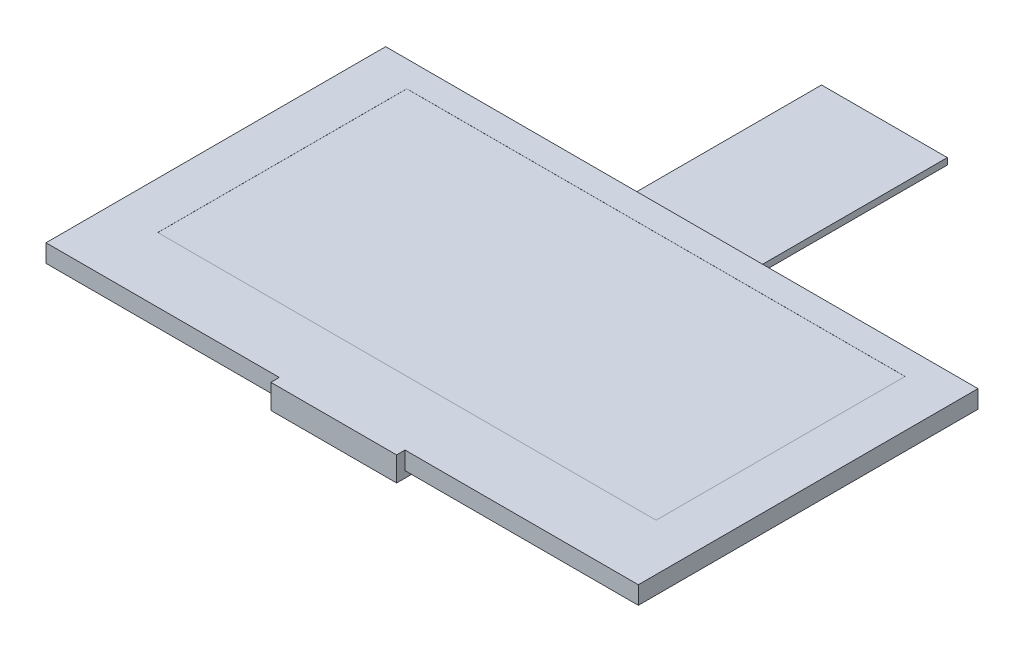
SolidWorks part; units mm, degrees
ref_plane "前视基准面" through (0, 0, 0) normal (0, 0, 1) x (1, 0, 0)
ref_plane "上视基准面" through (0, 0, 0) normal (0, 1, 0) x (1, 0, 0)
ref_plane "右视基准面" through (0, 0, 0) normal (1, 0, 0) x (0, 0, -1)
sketch "草图1" plane through (0, 0, 0) normal (0, 1, 0) x (1, 0, 0)
  line L1 (-36.5, -20.93) -> (36.5, -20.93)
  line L2 (-36.5, -20.93) -> (-36.5, 20.93)
  line L3 (-36.5, 20.93) -> (36.5, 20.93)
  line L4 (36.5, -20.93) -> (36.5, 20.93)
  line L5 (-36.5, -20.93) -> (36.5, 20.93) construction
  line L6 (-36.5, 20.93) -> (36.5, -20.93) construction
  point P0 (0, 0)
  dimension "D1" = 41.86
  dimension "D2" = 73
extrude "凸台-拉伸1" add sketch "草图1" along normal blind 2.2
sketch "草图2" plane through (0, 2.2, 0) normal (0, 1, 0) x (1, 0, 0)
  line L0 (36.5, 20.93) -> (-36.5, 20.93) construction
  line L1 (-30.705, -12.95) -> (30.705, -12.95)
  line L2 (-30.705, -12.95) -> (-30.705, 17.74)
  line L3 (-30.705, 17.74) -> (30.705, 17.74)
  line L4 (30.705, -12.95) -> (30.705, 17.74)
  line L5 (-30.705, -12.95) -> (30.705, 17.74) construction
  line L6 (-30.705, 17.74) -> (30.705, -12.95) construction
  point P0 (0, 2.395)
  point P6 (0, 4.3232)
  point P7 (0, 0)
  point P10 (0, 20.93)
  dimension "D1" = 30.69
  dimension "D2" = 61.41
  dimension "D3" = 3.19
extrude "切除-拉伸1" cut sketch "草图2" against normal blind 0.01 contours L2 L3 L4 L1
sketch "草图3" plane through (0, 2.2, 0) normal (0, 1, 0) x (1, 0, 0)
  line L0 (36.5, 20.93) -> (-36.5, 20.93) construction
  line L1 (-7.75, 20.93) -> (7.75, 20.93)
  line L2 (-7.75, 20.93) -> (-7.75, 45.9)
  line L3 (-7.75, 45.9) -> (7.75, 45.9)
  line L4 (7.75, 20.93) -> (7.75, 45.9)
  line L5 (-36.5, -20.93) -> (36.5, -20.93) construction
  line L6 (-7.75, -21.97) -> (7.75, -21.97)
  line L7 (-7.75, -21.97) -> (-7.75, -19.89)
  line L8 (-7.75, -19.89) -> (7.75, -19.89)
  line L9 (7.75, -21.97) -> (7.75, -19.89)
  line L10 (-7.75, -21.97) -> (7.75, -19.89) construction
  line L11 (-7.75, -19.89) -> (7.75, -21.97) construction
  point P6 (0, 20.93)
  point P8 (0, -20.93)
  dimension "D1" = 24.97
  dimension "D2" = 0
  dimension "D3" = 15.5
  dimension "D4" = 67.87
extrude "凸台-拉伸2" add sketch "草图3" against normal blind 3 contours L6 L9 L8 L7
extrude "凸台-拉伸3" add sketch "草图3<3>" along normal up to surface (-2.2 mm away) from surface up to face at (0, 0, 10.205) starting at face at (0, -0.8, 20.93)
sketch "草图3<3>" plane through (0, 2.2, 0) normal (0, 1, 0) x (1, 0, 0) same geometry as "草图3"
